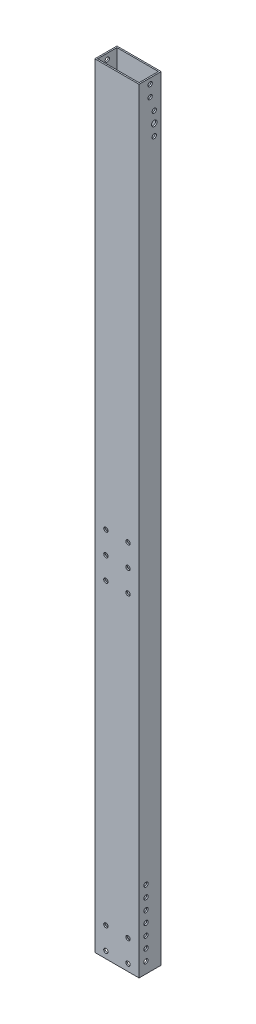
SolidWorks part; units mm, degrees
material "6061-T6 (SS)"
ref_plane "Front Plane" through (0, 0, 0) normal (0, 0, 1) x (1, 0, 0)
ref_plane "Top Plane" through (0, 0, 0) normal (0, 1, 0) x (1, 0, 0)
ref_plane "Right Plane" through (0, 0, 0) normal (1, 0, 0) x (0, 0, -1)
sketch "Sketch1" plane through (0, 0, 0) normal (0, 0, 1) x (1, 0, 0)
  line L1 (-25.4, -444.5) -> (25.4, -444.5)
  line L2 (-25.4, -444.5) -> (-25.4, 444.5)
  line L3 (-25.4, 444.5) -> (25.4, 444.5)
  line L4 (25.4, -444.5) -> (25.4, 444.5)
  line L5 (-25.4, -444.5) -> (25.4, 444.5) construction
  line L6 (-25.4, 444.5) -> (25.4, -444.5) construction
  point P0 (0, 0)
  dimension "D1" = 50.8
  dimension "D2" = 889
extrude "Boss-Extrude1" add sketch "Sketch1" along normal mid plane 25.4
shell "Shell1" thickness 1.5875 removed face at (0, -444.5, 0) removed face at (0, 444.5, 0)
sketch "Sketch3" plane through (0, 0, 0) normal (1, 0, 0) x (0, 0, -1)
  line L0 (-12.7, -444.5) -> (12.7, -444.5) construction
  line L1 (-12.7, 444.5) -> (12.7, 444.5) construction
  circle A0 centre (0, 425.45) radius 2.4892
  circle A1 centre (0, 438.15) radius 2.4892
  point P6 (0, -444.5)
  dimension "D1" = 4.9784
  dimension "D2" = 6.35
  dimension "D3" = 12.7
extrude "Cut-Extrude1" cut sketch "Sketch3" against normal through all both and the other way through all
sketch "Sketch4" plane through (0, 0, 0) normal (1, 0, 0) x (0, 0, -1)
  line L0 (12.7, 444.5) -> (12.7, -444.5) construction
  line L3 (-12.7, 444.5) -> (12.7, 444.5) construction
  circle A0 centre (4.7625, 396.875) radius 3.175
  circle A1 centre (4.7625, 409.575) radius 2.4892
  circle A2 centre (4.7625, 384.175) radius 2.4892
  dimension "D1" = 6.35
  dimension "D4" = 4.9784
  dimension "D2" = 7.9375
  dimension "D5" = 12.7
  dimension "D6" = 12.7
  dimension "D3" = 47.625
extrude "Cut-Extrude2" cut sketch "Sketch4" against normal through all both and the other way through all
sketch "Sketch5" plane through (0, 0, 0) normal (0, 0, 1) x (1, 0, 0)
  line L1 (-15.875, 410.3687) -> (15.875, 410.3687)
  line L2 (-15.875, 410.3687) -> (-15.875, 383.3812)
  line L3 (-15.875, 383.3812) -> (15.875, 383.3812)
  line L4 (15.875, 410.3687) -> (15.875, 383.3812)
  line L6 (25.4, 444.5) -> (-25.4, 444.5) construction
  point P4 (-15.875, 396.875)
  point P8 (0, 410.3687)
  point P9 (0, 444.5)
  dimension "D1" = 31.75
  dimension "D2" = 26.9875
  dimension "D3" = 47.625
extrude "Cut-Extrude3" cut sketch "Sketch5" against normal through all
fillet "Fillet1" radius 3.175 4 edges at (15.875, 410.3687, -11.9062) (15.875, 383.3812, -11.9062) (-15.875, 383.3812, -11.9062) (-15.875, 410.3687, -11.9062)
sketch "Sketch6" plane through (0, 0, 0) normal (0, 0, 1) x (1, 0, 0)
  line L0 (-25.4, 444.5) -> (-25.4, -444.5) construction
  line L1 (-25.4, -444.5) -> (25.4, -444.5) construction
  circle A0 centre (-12.7, -17.4625) radius 2.4892
  circle A1 centre (12.7, -17.4625) radius 2.4892
  circle A2 centre (12.7, -42.8625) radius 2.4892
  circle A3 centre (12.7, -68.2625) radius 2.4892
  circle A4 centre (-12.7, -42.8625) radius 2.4892
  circle A5 centre (-12.7, -68.2625) radius 2.4892
  circle A6 centre (-12.7, -436.5625) radius 2.4892
  circle A7 centre (12.7, -436.5625) radius 2.4892
  circle A8 centre (12.7, -411.1625) radius 2.4892
  circle A9 centre (-12.7, -411.1625) radius 2.4892
  dimension "D1" = 4.9784
  dimension "D3" = 427.0375
  dimension "D7" = 25.4
  dimension "D2" = 12.7
  dimension "D6" = 25.4
  dimension "D8" = 7.9375
  dimension "D9" = 12.7
  dimension "D12" = 25.4
  dimension "D13" = 25.4
  dimension "D4" = 2
  dimension "D5" = 3
  dimension "D10" = 2
  dimension "D11" = 2
extrude "Cut-Extrude4" cut sketch "Sketch6" along normal through all both and the other way through all
sketch "Sketch7" plane through (0, 0, 0) normal (1, 0, 0) x (0, 0, -1)
  line L0 (-12.7, -444.5) -> (12.7, -444.5) construction
  line L2 (-12.7, -444.5) -> (-12.7, 444.5) construction
  circle A0 centre (-4.7625, -431.8) radius 2.4892
  circle A1 centre (-4.7625, -419.1) radius 2.4892
  circle A2 centre (-4.7625, -406.4) radius 2.4892
  circle A3 centre (-4.7625, -393.7) radius 2.4892
  circle A4 centre (-4.7625, -381) radius 2.4892
  circle A5 centre (-4.7625, -368.3) radius 2.4892
  circle A6 centre (-4.7625, -355.6) radius 2.4892
  dimension "D1" = 4.9784
  dimension "D5" = 12.7
  dimension "D2" = 12.7
  dimension "D3" = 7.9375
  dimension "D4" = 7
extrude "Cut-Extrude5" cut sketch "Sketch7" against normal through all both and the other way through all
equation "\"D6@Sketch4\"=\"D5@Sketch4\""
